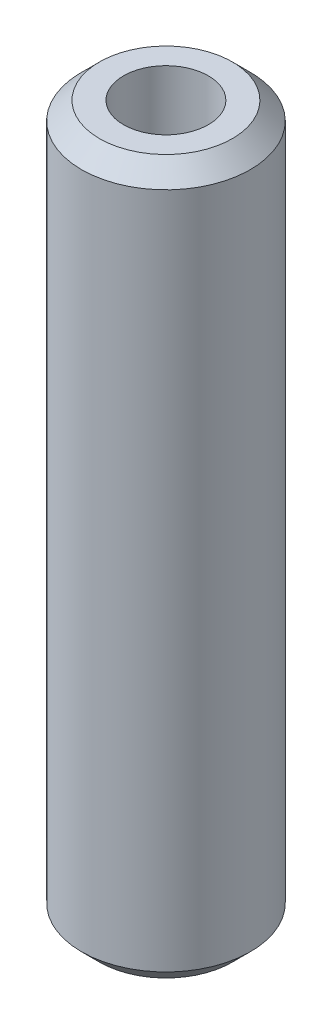
SolidWorks part; units mm, degrees
ref_plane "Front Plane" through (0, 0, 0) normal (0, 0, 1) x (1, 0, 0)
ref_plane "Top Plane" through (0, 0, 0) normal (0, 1, 0) x (1, 0, 0)
ref_plane "Right Plane" through (0, 0, 0) normal (1, 0, 0) x (0, 0, -1)
sketch "Sketch1" plane through (0, 0, 0) normal (0, 1, 0) x (1, 0, 0)
  circle A0 centre (0, 0) radius 20
  dimension "SHAFT_OD" = 40
extrude "Boss-Extrude1" add sketch "Sketch1" along normal blind 169.042
sketch "Sketch2" plane through (0, 0, 0) normal (0, 1, 0) x (1, 0, 0)
  circle A0 centre (0, 0) radius 10.0498
  dimension "BORE_D" = 20.0996
extrude "Cut-Extrude1" cut sketch "Sketch2" along normal through all
chamfer "Chamfer1" distance 4.2461 angle 45 2 edges at (0, 169.042, 20) (0, 0, 20)
